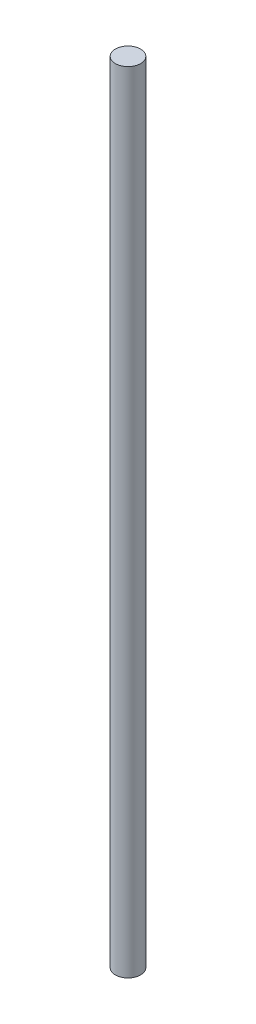
SolidWorks part; units mm, degrees
material "Chrome Stainless Steel"
ref_plane "Front Plane" through (0, 0, 0) normal (0, 0, 1) x (1, 0, 0)
ref_plane "Top Plane" through (0, 0, 0) normal (0, 1, 0) x (1, 0, 0)
ref_plane "Right Plane" through (0, 0, 0) normal (1, 0, 0) x (0, 0, -1)
sketch "Sketch1" plane through (0, 0, 0) normal (0, 1, 0) x (1, 0, 0)
  circle A0 centre (0, 0) radius 3.175
extrude "Boss-Extrude1" add sketch "Sketch1" along normal blind 198.575
